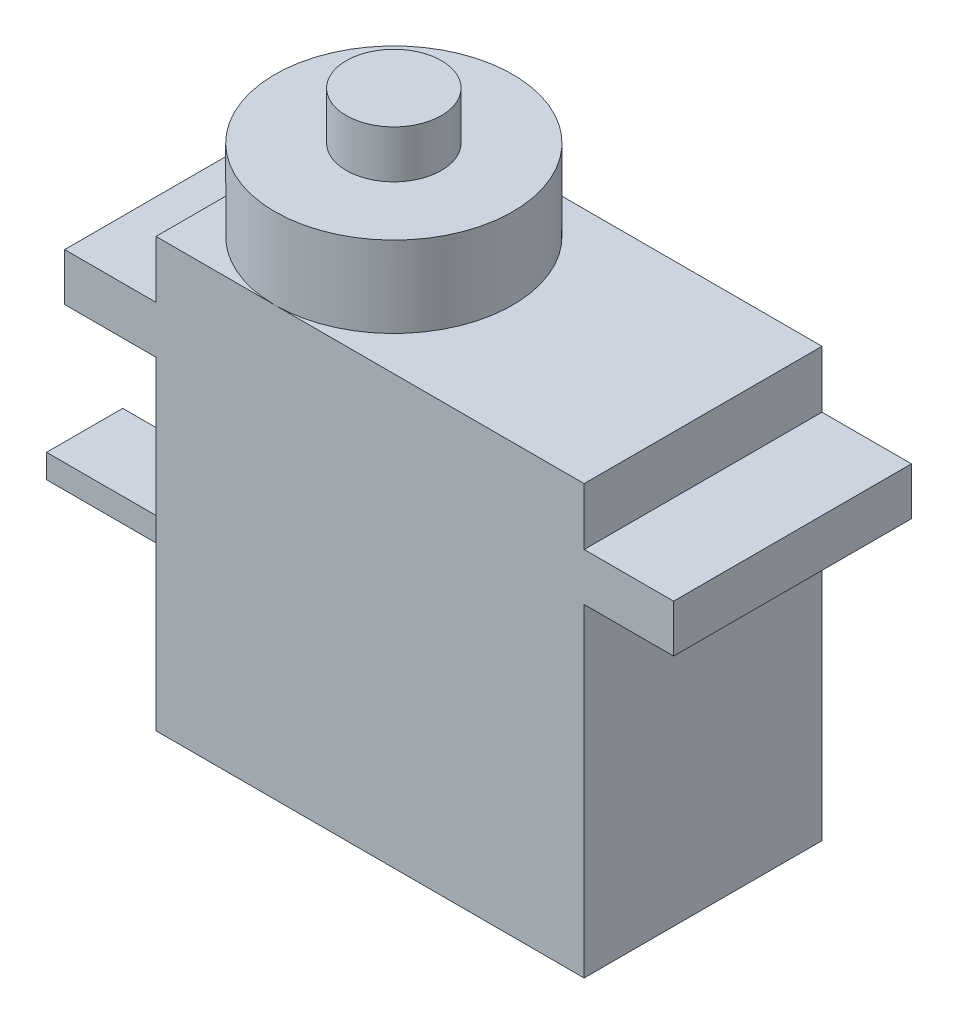
SolidWorks part; units mm, degrees
ref_plane "Front Plane" through (0, 0, 0) normal (0, 0, 1) x (1, 0, 0)
ref_plane "Top Plane" through (0, 0, 0) normal (0, 1, 0) x (1, 0, 0)
ref_plane "Right Plane" through (0, 0, 0) normal (1, 0, 0) x (0, 0, -1)
sketch "Sketch1" plane through (0, 0, 0) normal (0, 1, 0) x (1, 0, 0)
  line L1 (0, 0) -> (22.5, 0)
  line L2 (0, 0) -> (0, 12.5)
  line L3 (0, 12.5) -> (22.5, 12.5)
  line L4 (22.5, 0) -> (22.5, 12.5)
  line L5 (0, 0) -> (22.5, 12.5) construction
  line L6 (0, 12.5) -> (22.5, 0) construction
  line L7 (0, 0) -> (-4.8, 0)
  line L8 (0, 0) -> (0, 12.5)
  line L9 (0, 12.5) -> (-4.8, 12.5)
  line L10 (-4.8, 0) -> (-4.8, 12.5)
  line L11 (0, 0) -> (-4.8, 12.5) construction
  line L12 (0, 12.5) -> (-4.8, 0) construction
  line L13 (22.5, 0) -> (27.2, 0)
  line L14 (22.5, 0) -> (22.5, 12.5)
  line L15 (22.5, 12.5) -> (27.2, 12.5)
  line L16 (27.2, 0) -> (27.2, 12.5)
  line L17 (22.5, 0) -> (27.2, 12.5) construction
  line L18 (22.5, 12.5) -> (27.2, 0) construction
  point P4 (11.25, 6.25)
  point P8 (-2.4, 6.25)
  point P11 (24.85, 6.25)
  dimension "D1" = 12.5
  dimension "D2" = 22.5
  dimension "D3" = 32
  dimension "D4" = 4.8
extrude "Boss-Extrude1" add sketch "Sketch1" along normal blind 22.5 contours L1 L4 L3 L2 region at (11.25, 0, -6.25)
extrude "Boss-Extrude2" add sketch "Sketch1<3>" along normal blind 2.5 from offset 17 contours L10 L7 L2 L9 | L13 L16 L15 L4 region at (-2.4, 0, -6.25) region at (24.85, 0, -6.25)
sketch "Sketch1<3>" plane through (0, 0, 0) normal (0, 1, 0) x (1, 0, 0) same geometry as "Sketch1"
sketch "Sketch2" plane through (0, 22.5, 0) normal (0, 1, 0) x (1, 0, 0)
  line L0 (0, 0) -> (0, 12.5) construction
  line L1 (0, 0) -> (22.5, 0) construction
  circle A0 centre (6.25, 6.25) radius 2.5
  circle A1 centre (6.25, 6.25) radius 6.25
  dimension "D3" = 5
  dimension "D1" = 6.25
  dimension "D2" = 6.25
  dimension "D4" = 3.75
extrude "Boss-Extrude3" add sketch "Sketch2" along normal blind 4.25 contours A0 | A1 A0 region at (6.25, 22.5, -6.25) region at (0.1768, 22.5, -6.25)
extrude "Boss-Extrude4" add sketch "Sketch2<3>" along normal blind 6.75 contours A0 region at (6.25, 22.5, -6.25)
sketch "Sketch2<3>" plane through (0, 22.5, 0) normal (0, 1, 0) x (1, 0, 0) same geometry as "Sketch2"
sketch "Sketch3" plane through (0, 0, 0) normal (-1, 0, 0) x (0, 0, 1)
  line L0 (0, 0) -> (-12.5, 0) construction
  line L1 (-8.25, 4.3) -> (-4.25, 4.3)
  line L2 (-8.25, 4.3) -> (-8.25, 5.55)
  line L3 (-8.25, 5.55) -> (-4.25, 5.55)
  line L4 (-4.25, 4.3) -> (-4.25, 5.55)
  line L5 (-8.25, 4.3) -> (-4.25, 5.55) construction
  line L6 (-8.25, 5.55) -> (-4.25, 4.3) construction
  line L7 (-12.5, 17) -> (-12.5, 0) construction
  point P4 (-6.25, 4.925)
  dimension "D1" = 4.3
  dimension "D2" = 1.25
  dimension "D3" = 4
  dimension "D4" = 6.25
extrude "Boss-Extrude5" add sketch "Sketch3" along normal blind 10
